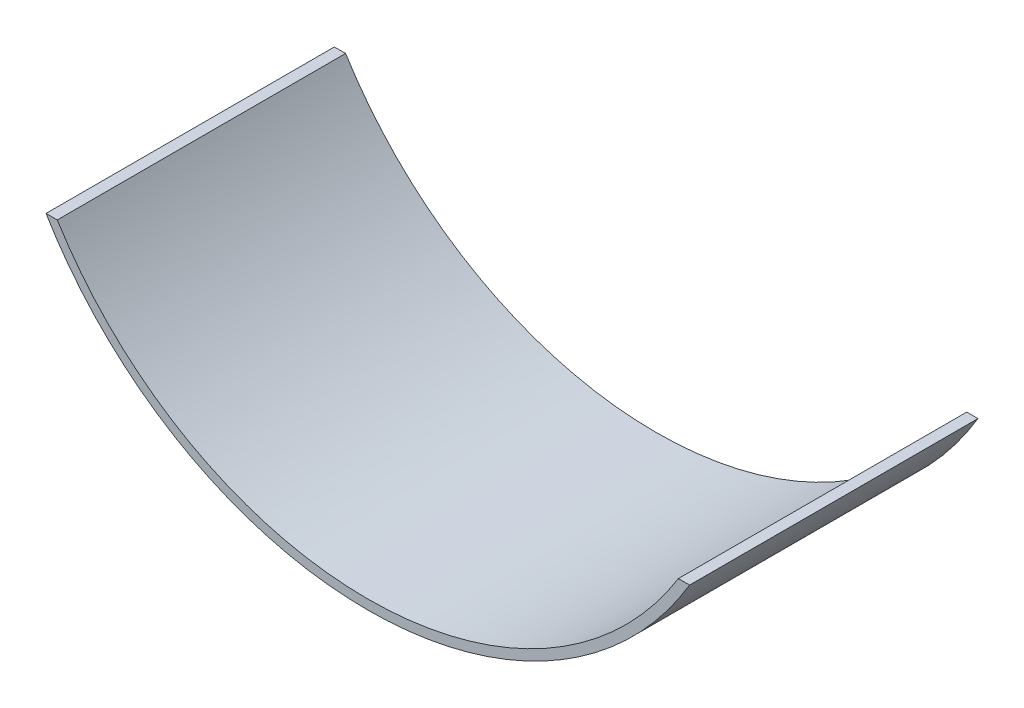
SolidWorks part; units mm, degrees
ref_plane "前视基准面" through (0, 0, 0) normal (0, 0, 1) x (1, 0, 0)
ref_plane "上视基准面" through (0, 0, 0) normal (0, 1, 0) x (1, 0, 0)
ref_plane "右视基准面" through (0, 0, 0) normal (1, 0, 0) x (0, 0, -1)
sketch "草图1" plane through (0, 0, 0) normal (0, 0, 1) x (1, 0, 0)
  line L1 (0, -100) -> (167.4067, -100)
  line L2 (167.4067, -100) -> (-167.4067, -100)
  arc A0 (-167.4067, -100) -> (167.4067, -100) centre (0, 0) ccw
  arc A2 (-161.5549, -100) -> (161.5549, -100) centre (0, 0) ccw
extrude "凸台-拉伸2" add sketch "草图1" along normal blind 150 contours L2 A0 L1 region at (164.4808, -103.4803, 0)
sketch "草图2" plane through (0, 0, 0) normal (0, 0, -1) x (-1, 0, 0)
  line L0 (-167.4067, -100) -> (167.4067, -100)
  arc A0 (-167.4067, -100) -> (167.4067, -100) centre (0, 0) ccw
extrude "凸台-拉伸3" add sketch "草图2" along normal blind 10
sketch "草图3" plane through (0, 0, 150) normal (0, 0, 1) x (1, 0, 0)
  line L0 (-167.4067, -100) -> (167.4067, -100)
  arc A0 (-167.4067, -100) -> (167.4067, -100) centre (0, 0) ccw
extrude "凸台-拉伸4" add sketch "草图3" along normal blind 5
sketch "草图4" plane through (0, 0, -10) normal (0, 0, -1) x (-1, 0, 0)
  line L0 (0, 0) -> (0, -211.2543)
  line L8 (-25, -150.2939) -> (25, -150.2939)
  line L9 (-25, -150.2939) -> (-25, -136.2939)
  line L10 (-25, -136.2939) -> (25, -136.2939)
  line L11 (25, -150.2939) -> (25, -136.2939)
  line L12 (-25, -150.2939) -> (25, -136.2939) construction
  line L13 (-25, -136.2939) -> (25, -150.2939) construction
  point P3 (0, -147.0628)
  point P8 (0, -143.2939)
extrude "切除-拉伸1" cut sketch "草图4" against normal blind 8 contours L10 L9 L8 L0 | L8 L11 L10 L0 region at (-12.5, -143.2939, -10) region at (12.5, -143.2939, -10)
fillet "圆角1" radius 15 1 edges at (0, -136.2939, -2)
fillet "圆角2" radius 3 1 edges at (0, -136.2939, -10)
fillet "圆角3" radius 1 3 edges at (0, -150.2939, -10) (-25, -142.4439, -10) (25, -142.4439, -10)
sketch "草图5" plane through (0, -100, 0) normal (0, 1, 0) x (1, 0, 0)
  line L0 (-167.4067, 10) -> (167.4067, 10)
  line L1 (167.4067, 10) -> (167.4067, 0)
  line L2 (167.4067, -155) -> (167.4067, 10) construction
  line L3 (167.4067, 0) -> (-167.4067, 0)
  line L4 (-167.4067, -155) -> (-167.4067, 10) construction
  line L5 (-167.4067, 0) -> (-167.4067, 10)
extrude "切除-拉伸3" cut sketch "草图5" against normal blind 474
sketch "草图6" plane through (0, -100, 0) normal (0, 1, 0) x (1, 0, 0)
  line L0 (-167.4067, -155) -> (167.4067, -155)
  line L1 (167.4067, -155) -> (167.4067, -150)
  line L2 (167.4067, -150) -> (-167.4067, -150)
  line L3 (-167.4067, -155) -> (-167.4067, 0) construction
  line L4 (-167.4067, -150) -> (-167.4067, -155)
extrude "切除-拉伸4" cut sketch "草图6" against normal blind 474
